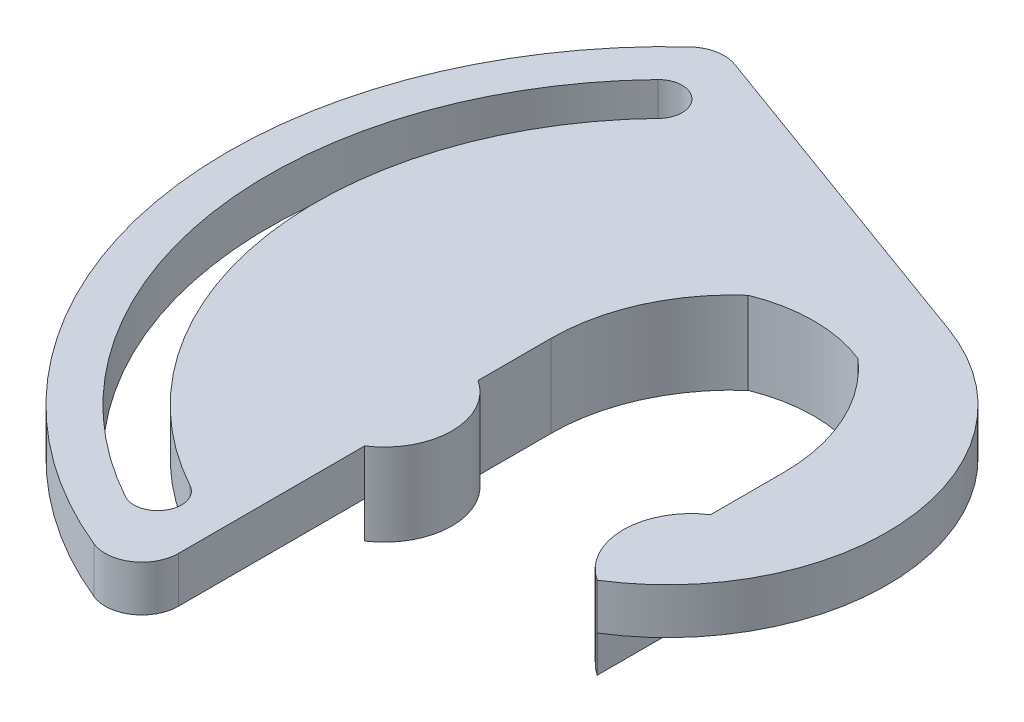
SolidWorks part; units mm, degrees
material "ABS"
ref_plane "Front Plane" through (0, 0, 0) normal (0, 0, 1) x (1, 0, 0)
ref_plane "Top Plane" through (0, 0, 0) normal (0, 1, 0) x (1, 0, 0)
ref_plane "Right Plane" through (0, 0, 0) normal (1, 0, 0) x (0, 0, -1)
sketch "Sketch1" plane through (0, 0, 0) normal (0, 1, 0) x (1, 0, 0)
  line L0 (0, -8) -> (0, 8) construction
  line L1 (-6.35, 0) -> (6.35, 0) construction
  line L2 (-6.35, 0) -> (-6.35, -6.3779)
  line L3 (6.35, -6.3779) -> (6.35, 0)
  arc A0 (-3, 7.4162) -> (3, 7.4162) centre (0, 0) cw
  arc A1 (-3, -7.4162) -> (3, -7.4162) centre (0, 0) ccw construction
  arc A2 (-3, 7.4162) -> (-3, -7.4162) centre (3.534, 0) ccw construction
  arc A3 (-3, 7.4162) -> (-6.35, 0) centre (3.534, 0) ccw
  arc A4 (3, 7.4162) -> (6.35, 0) centre (-3.534, 0) cw
  arc A5 (-6.35, -6.3779) -> (6.35, -6.3779) centre (0, 0) cw
  dimension "D4" = 1
  dimension "D1" = 12.7
  dimension "D2" = 8
  dimension "D3" = 3
extrude "Boss-Extrude1" add sketch "Sketch1" along normal blind 2
sketch "Sketch2" plane through (0, 2, 0) normal (0, 1, 0) x (1, 0, 0)
  line L0 (4.1042, 11.2763) -> (-15.4269, 18.3851)
  line L4 (-6.35, -23.1447) -> (-6.35, -6.3779)
  line L5 (0, 0) -> (-15.4269, 18.3851) construction
  line L7 (0, 0) -> (0, -7.7251) construction
  line L10 (-6.35, -6.3779) -> (-6.35, 0)
  line L11 (6.35, 0) -> (6.35, -6.3779)
  line L12 (-6.35, -6.3779) -> (-6.35, 0)
  line L13 (6.35, 0) -> (6.35, -10.1822)
  arc A0 (6.35, -10.1822) -> (4.1042, 11.2763) centre (0, 0) ccw
  arc A6 (-6.35, -23.1447) -> (-15.4269, 18.3851) centre (0, 0) cw
  arc A12 (6.35, -6.3779) -> (-6.35, -6.3779) centre (0, 0) ccw
  arc A13 (6.35, 0) -> (3, 7.4162) centre (-3.534, 0) ccw
  arc A14 (3, 7.4162) -> (-3, 7.4162) centre (0, 0) ccw
  arc A15 (-3, 7.4162) -> (-6.35, 0) centre (3.534, 0) ccw
  arc A17 (6.35, 0) -> (3, 7.4162) centre (-3.534, 0) ccw
  arc A18 (3, 7.4162) -> (-3, 7.4162) centre (0, 0) ccw
  arc A19 (-3, 7.4162) -> (-6.35, 0) centre (3.534, 0) ccw
  dimension "D1" = 24
  dimension "D4" = 12
  dimension "D2" = 140
  dimension "D3" = 0
extrude "Boss-Extrude2" add sketch "Sketch2" along normal blind 2.5 separate body
fillet "Fillet1" radius 2 2 edges at (-6.35, 3.25, 23.1447) (-15.4269, 3.25, -18.3851)
ref_axis "Axis1" through (0, -0.25, 0) along (0, 1, 0)
sketch "Sketch3" plane through (0, 4.5, 0) normal (0, 1, 0) x (1, 0, 0)
  line L0 (-18.9833, -2.8767) -> (-20.2686, -3.0715) construction
  line L1 (-21.5539, -3.2662) -> (-20.2686, -3.0715) construction
  line L2 (-14.74, 14.2472) -> (-11.9601, 17.1233) construction
  line L3 (-9.8572, -17.9746) -> (0, 0) construction
  line L4 (0, 0) -> (-14.74, 14.2472) construction
  line L5 (-9.8572, -17.9746) -> (-6.35, -19.8979) construction
  line L7 (-6.35, -20.3538) -> (-6.35, 0) construction
  line L8 (4.1042, 11.2763) -> (-14.3099, 17.9785) construction
  arc A0 (-9.8572, -17.9746) -> (-14.74, 14.2472) centre (0, 0) cw construction
  arc A1 (-9.2321, -16.8347) -> (-10.4823, -19.1144) centre (-9.8572, -17.9746) cw
  arc A2 (-15.6748, 15.1506) -> (-13.8053, 13.3437) centre (-14.74, 14.2472) cw
  arc A3 (-15.6748, 15.1506) -> (-10.4823, -19.1144) centre (0, 0) ccw
  arc A4 (-13.8053, 13.3437) -> (-9.2321, -16.8347) centre (0, 0) ccw
  dimension "D1" = 1.3
  dimension "D2" = 4
  dimension "D4" = 20.5
  dimension "D3" = 1.3
extrude "Cut-Extrude1" cut sketch "Sketch3" against normal through all
sketch "Sketch4" plane through (0, 2, 0) normal (0, -1, 0) x (1, 0, 0)
  arc A0 (-9.8572, 17.9746) -> (-14.74, -14.2472) centre (0, 0) ccw construction
  arc A1 (-9.8572, 17.9746) -> (-14.74, -14.2472) centre (0, 0) ccw
sketch "Sketch6" plane through (0, 4.5, 0) normal (0, 1, 0) x (1, 0, 0)
  line L0 (6.35, -10.1822) -> (6.35, -3.9925)
  line L1 (6.35, 0) -> (6.35, -10.1822) construction
  line L2 (6.35, 0) -> (3, -7.4162) construction
  line L3 (3, -7.4162) -> (3, 7.4162) construction
  line L4 (6.35, 0) -> (3, 7.4162) construction
  arc A0 (6.35, -10.1822) -> (6.35, -3.9925) centre (8.3725, -7.0873) cw
extrude "Boss-Extrude3" add sketch "Sketch6" against normal up to surface (4.5 mm away) up to face at (0, 0, -3.1266)
mirror "Mirror1" about plane through (0, 0, 0) normal (1, 0, 0) of "Boss-Extrude3"
